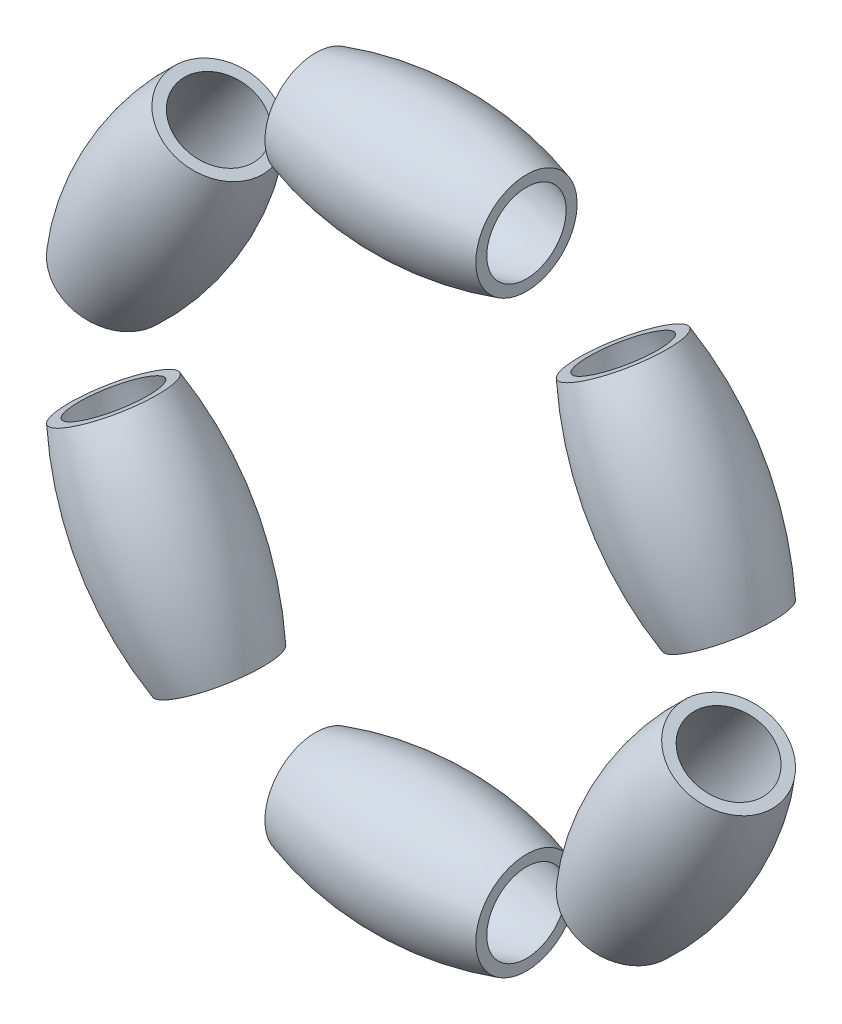
SolidWorks part; units mm, degrees
material "Rubber"
ref_plane "Front Plane" through (0, 0, 0) normal (0, 0, 1) x (1, 0, 0)
ref_plane "Top Plane" through (0, 0, 0) normal (0, 1, 0) x (1, 0, 0)
ref_plane "Right Plane" through (0, 0, 0) normal (1, 0, 0) x (0, 0, -1)
sketch "Master" plane through (0, 0, 0) normal (0, 0, 1) x (1, 0, 0)
  line L0 (0, 69) -> (0, -69) construction
  line L1 (68.4737, 0) -> (34.2369, 59.3)
  line L2 (34.2369, 59.3) -> (-34.2369, 59.3)
  line L3 (-34.2369, 59.3) -> (-68.4737, 0)
  line L4 (-68.4737, 0) -> (-34.2369, -59.3)
  line L5 (-34.2369, -59.3) -> (34.2369, -59.3)
  line L6 (34.2369, -59.3) -> (68.4737, 0)
  line L7 (20.1736, 65.985) -> (20.1736, -65.985)
  line L8 (-20.1736, 65.985) -> (-20.1736, -65.985)
  line L9 (-20.1736, -65.985) -> (20.1736, 65.985) construction
  line L10 (-18.1736, 64.4881) -> (-18.1736, -64.4881)
  line L11 (18.1736, 64.4881) -> (18.1736, -64.4881)
  line L12 (-24.1736, 59.3) -> (-24.1736, -59.3)
  line L13 (24.1736, 59.3) -> (24.1736, -59.3)
  line L14 (-24.1736, 56.3) -> (24.1736, 56.3)
  line L15 (-24.1736, -56.3) -> (24.1736, -56.3)
  line L16 (-68.4737, 0) -> (68.4737, 0) construction
  line L17 (-24.1736, 57.2) -> (24.1736, 57.2)
  line L18 (-24.1736, 55.4) -> (24.1736, 55.4)
  line L19 (-24.1736, -55.4) -> (24.1736, -55.4)
  line L20 (-24.1736, -57.2) -> (24.1736, -57.2)
  line L21 (-24.1736, 57.3) -> (24.1736, 57.3)
  line L22 (-24.1736, 55.3) -> (24.1736, 55.3)
  line L23 (-24.1736, -55.3) -> (24.1736, -55.3)
  line L24 (-24.1736, -57.3) -> (24.1736, -57.3)
  circle A0 centre (0, 0) radius 67
  circle A1 centre (0, 0) radius 59.3 construction
  circle A2 centre (0, 0) radius 69
  circle A3 centre (0, 0) radius 65
  point P2 (0, 0)
  point P12 (0, 0)
  point P18 (0, 0)
  point P21 (0, -67)
  point P22 (0, 67)
  point P24 (0, 67)
  point P25 (0, 67)
  point P29 (0, 67)
  point P39 (0, 0)
  point P48 (0, 0)
  point P66 (0, 0)
  point P74 (0, 0)
sketch "Sketch1" plane through (0, 0, 0) normal (0, 0, 1) x (1, 0, 0)
  line L0 (-20.1736, 65.985) -> (-20.1736, -65.985) construction
  line L1 (-20.1736, 65.985) -> (-20.1736, 63.8907)
  line L2 (20.1736, 65.985) -> (20.1736, -65.985) construction
  line L3 (20.1736, 65.985) -> (20.1736, 63.8907)
  line L4 (-24.1736, 56.3) -> (24.1736, 56.3) construction
  line L5 (-20.1736, 56.3) -> (20.1736, 56.3) construction
  line L6 (-20.1736, 63.8907) -> (-20.1736, 56.3) construction
  line L7 (20.1736, 63.8907) -> (20.1736, 56.3) construction
  circle A0 centre (0, 0) radius 67 construction
  arc A1 (20.1736, 63.8907) -> (-20.1736, 63.8907) centre (0, 0) ccw
  circle A2 centre (0, 0) radius 69 construction
  arc A3 (20.1736, 65.985) -> (-20.1736, 65.985) centre (0, 0) ccw
revolve "Skin" add sketch "Sketch1" angle 360 about L5
ref_axis "Axis1" through (0, 0, 0) along (0, 0, 1)
pattern_circular "CirPattern1" count 6 over 360 about axis through (0, 0, 0) along (0, 0, 1) of bodies 110
